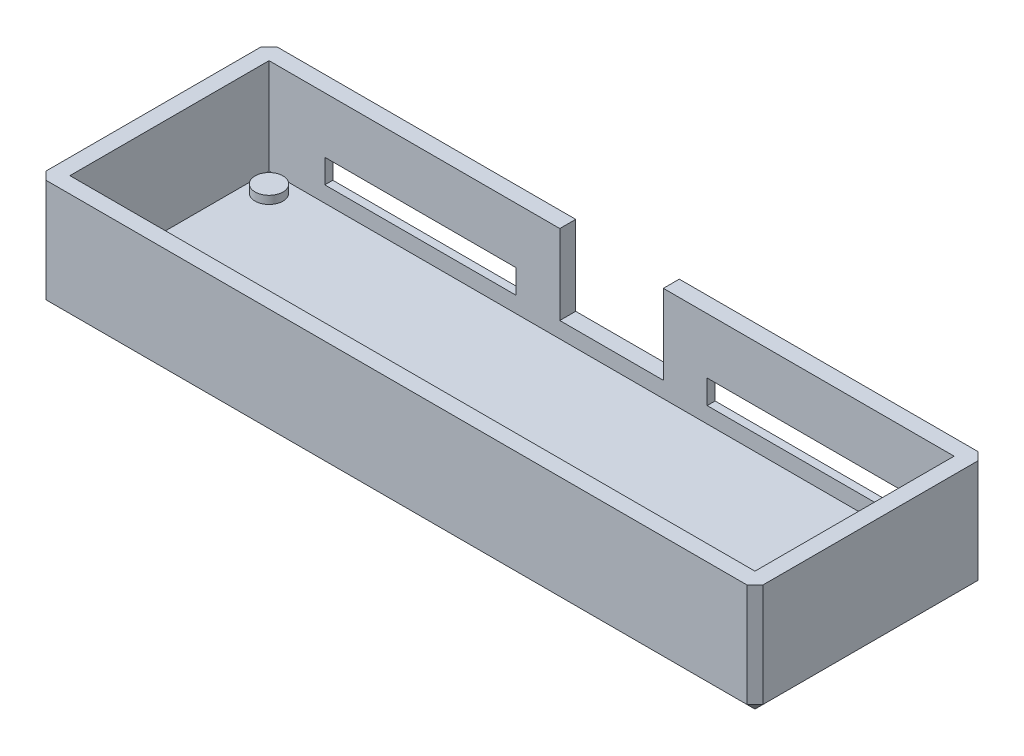
SolidWorks part; units mm, degrees
ref_plane "Front Plane" through (0, 0, 0) normal (0, 0, 1) x (1, 0, 0)
ref_plane "Top Plane" through (0, 0, 0) normal (0, 1, 0) x (1, 0, 0)
ref_plane "Right Plane" through (0, 0, 0) normal (1, 0, 0) x (0, 0, -1)
sketch "Sketch1" plane through (0, 0, 0) normal (0, 1, 0) x (1, 0, 0)
  line L0 (-43, 0) -> (-45, 0) construction
  line L1 (-45, -14.5) -> (45, -14.5)
  line L2 (-45, -14.5) -> (-45, 14.5)
  line L3 (-45, 14.5) -> (45, 14.5)
  line L4 (45, -14.5) -> (45, 14.5)
  line L5 (-45, -14.5) -> (45, 14.5) construction
  line L6 (-45, 14.5) -> (45, -14.5) construction
  line L7 (-43, -12.5) -> (43, -12.5)
  line L8 (-43, -12.5) -> (-43, 12.5)
  line L9 (-43, 12.5) -> (43, 12.5)
  line L10 (43, -12.5) -> (43, 12.5)
  line L11 (-43, -12.5) -> (43, 12.5) construction
  line L12 (-43, 12.5) -> (43, -12.5) construction
  line L13 (0, 12.5) -> (0, 14.5) construction
  point P0 (0, 0)
  point P6 (0, 0)
  dimension "D1" = 2
  dimension "D2" = 86
  dimension "D3" = 25
extrude "Boss-Extrude1" add sketch "Sketch1" along normal blind 12
extrude "Boss-Extrude2" add sketch "Sketch1<2>" against normal blind 2 contours L7 L10 L9 L8 | L1 L4 L3 L2 L10 L7 L8 L9 region at (-44.0544, 0, 0) region at (0, 0, 0)
sketch "Sketch1<2>" plane through (0, 0, 0) normal (0, 1, 0) x (1, 0, 0) same geometry as "Sketch1"
sketch "Sketch2" plane through (0, 0, 0) normal (0, 1, 0) x (1, 0, 0)
  line L0 (40.6, -12) -> (40.6, -10.1) construction
  line L1 (-42.5, -12) -> (42.5, -12) construction
  line L2 (-42.5, -12) -> (-42.5, 12) construction
  line L3 (-42.5, 12) -> (42.5, 12) construction
  line L4 (42.5, -12) -> (42.5, 12) construction
  line L5 (-42.5, -12) -> (42.5, 12) construction
  line L6 (-42.5, 12) -> (42.5, -12) construction
  line L7 (40.6, -10.1) -> (42.5, -10.1) construction
  line L8 (0, -12) -> (0, 12) construction
  circle A0 centre (40.6, -10.1) radius 1
  circle A1 centre (-40.6, -10.1) radius 1
  point P0 (0, 0)
  point P13 (0, 0)
  dimension "D3" = 2
  dimension "D1" = 85
  dimension "D2" = 24
  dimension "D4" = 1.9
extrude "Boss-Extrude3" add sketch "Sketch2" along normal blind 2.65
sketch "Sketch3" plane through (0, 0, 0) normal (0, 1, 0) x (1, 0, 0)
  circle A0 centre (40.6, -10.1) radius 1.75
  circle A1 centre (-40.6, -10.1) radius 1.75
  dimension "D1" = 3.5
extrude "Boss-Extrude4" add sketch "Sketch3" along normal blind 1
mirror "Mirror1" about plane through (0, 0, 0) normal (0, 0, 1) of "Boss-Extrude4"
chamfer "Chamfer1" distance 1 angle 45 8 edges at (45, 5, -14.5) (45, 5, 14.5) (45, -2, 0) (0, -2, 14.5) (-45, 5, 14.5) (-45, -2, 0) (0, -2, -14.5) (-45, 5, -14.5)
sketch "Sketch4" plane through (0, 0, -12.5) normal (0, 0, -1) x (-1, 0, 0)
  line L0 (-44, 12) -> (44, 12) construction
  line L1 (-6.5, 2) -> (6.5, 2)
  line L2 (-6.5, 2) -> (-6.5, 12)
  line L3 (-6.5, 12) -> (6.5, 12)
  line L4 (6.5, 2) -> (6.5, 12)
  line L5 (43, 0) -> (-43, 0) construction
  point P4 (0, 2)
  point P13 (0, 0)
  dimension "D1" = 13
  dimension "D3" = 2
extrude "Cut-Extrude1" cut sketch "Sketch4" along normal up to next
sketch "Sketch5" plane through (0, 0, -14.5) normal (0, 0, -1) x (-1, 0, 0)
  line L0 (-44, -1) -> (44, -1) construction
  line L1 (-36, 5) -> (-12, 5)
  line L2 (-36, 5) -> (-36, 2)
  line L3 (-36, 2) -> (-12, 2)
  line L4 (-12, 5) -> (-12, 2)
  line L5 (-36, 5) -> (-12, 2) construction
  line L6 (-36, 2) -> (-12, 5) construction
  point P0 (-24, 3.5)
  point P5 (0, 0)
  dimension "D1" = 24
  dimension "D2" = 24
  dimension "D3" = 3
  dimension "D4" = 3
extrude "Cut-Extrude2" cut sketch "Sketch5" against normal up to next
chamfer "Chamfer2" distance 1 angle 45 4 edges at (36, 3.5, -14.5) (24, 2, -14.5) (12, 3.5, -14.5) (24, 5, -14.5)
mirror "Mirror2" about plane through (0, 0, 0) normal (1, 0, 0) of "Chamfer2", "Cut-Extrude2"
